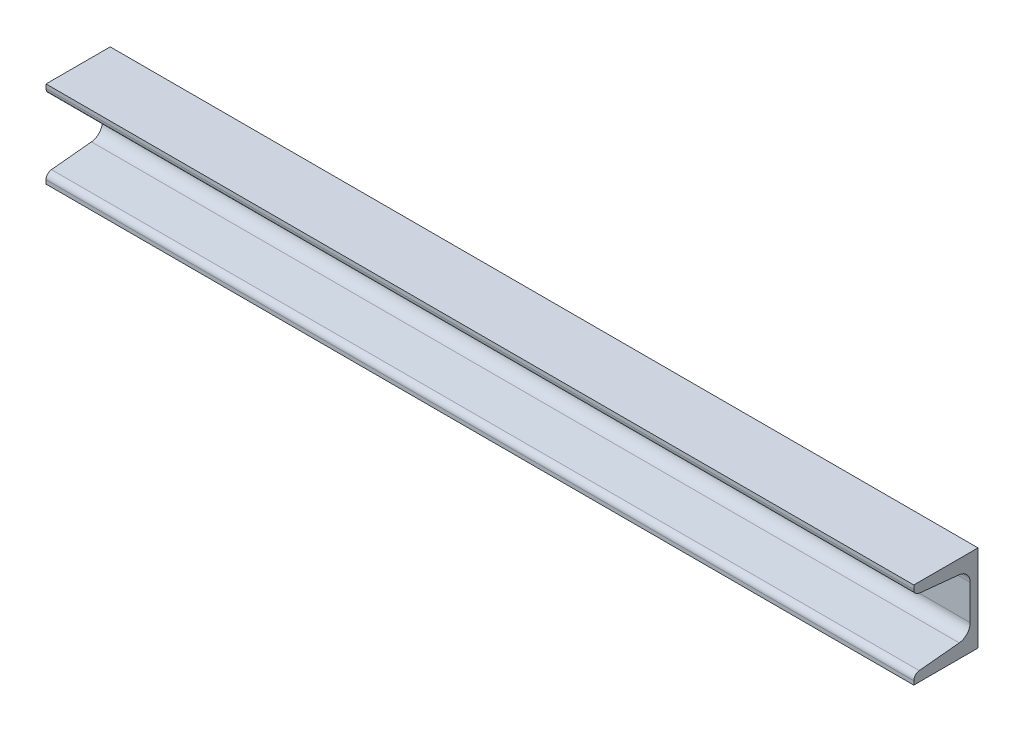
SolidWorks part; units mm, degrees
ref_plane "Front" through (0, 0, 0) normal (0, 0, 1) x (1, 0, 0)
ref_plane "Top" through (0, 0, 0) normal (0, 1, 0) x (1, 0, 0)
ref_plane "Right" through (0, 0, 0) normal (1, 0, 0) x (0, 0, -1)
sketch "Sketch1" plane through (0, 0, -28.2113) normal (1, 0, 0) x (0, 0, 1)
  line L0 (28.2113, -25) -> (28.2113, 25)
  line L1 (28.2113, 25) -> (65.2113, 25)
  line L2 (-69.1718, 0) -> (97.3831, 0) construction
  line L3 (32.7113, 16.375) -> (32.7113, -16.375)
  line L4 (32.7113, 16.375) -> (65.2113, 19.625)
  line L5 (65.2113, 19.625) -> (65.2113, 25)
  line L6 (32.7113, 16.375) -> (32.7113, 19.625) construction
  line L7 (32.7113, 19.625) -> (65.2113, 19.625) construction
  line L8 (48.9613, 25) -> (48.9613, 18) construction
  line L9 (65.2113, -19.625) -> (65.2113, -25)
  line L10 (28.2113, -25) -> (65.2113, -25)
  line L11 (32.7113, -16.375) -> (65.2113, -19.625)
  point P15 (28.2113, 0)
  point P16 (32.7113, 0)
  dimension "D6" = 3.25
  dimension "D1" = 16.25
extrude "Base" add sketch "Sketch1" along normal blind 500
fillet "Fillet1" radius 7 2 edges at (250, -16.375, 4.5) (250, 16.375, 4.5)
fillet "Fillet2" radius 3.5 2 edges at (250, -19.625, 37) (250, 19.625, 37)
equation "\"D1@Sketch1\" =  ( \"b@Sketch1\" - \"d@Sketch1\" )  / 2"
equation "\"D6@Sketch1\" = ( \"b@Sketch1\" - \"d@Sketch1\" )  / 10"
